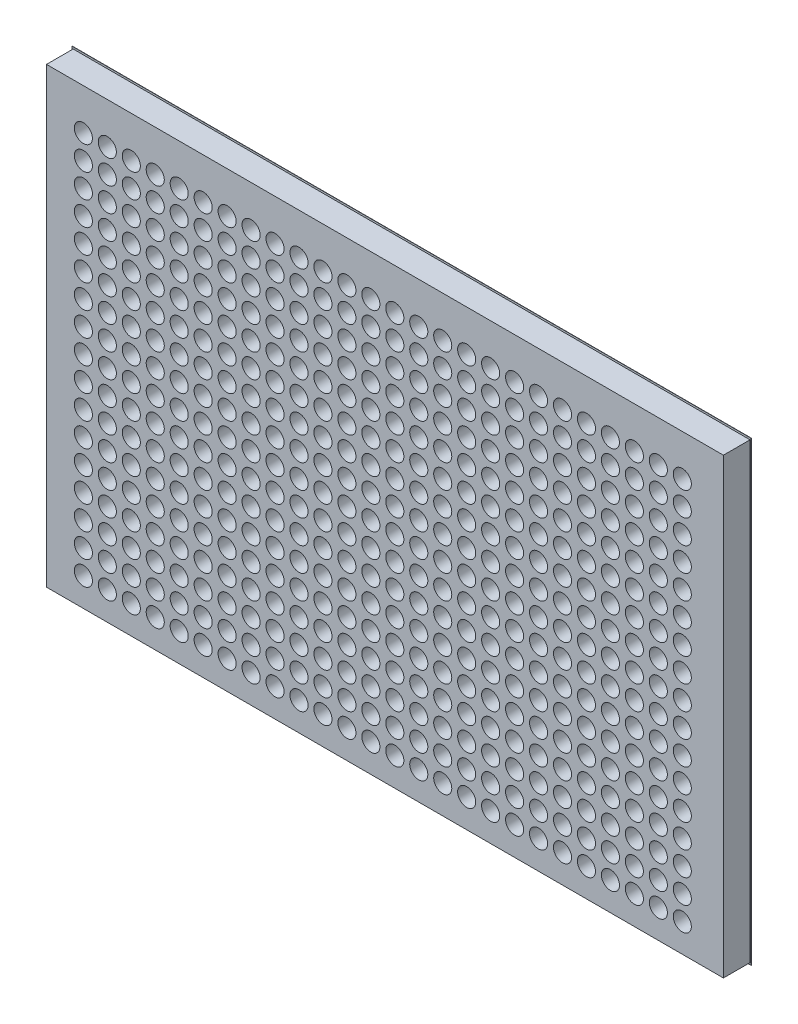
SolidWorks part; units mm, degrees
ref_plane "Front Plane" through (0, 0, 0) normal (0, 0, 1) x (1, 0, 0)
ref_plane "Top Plane" through (0, 0, 0) normal (0, 1, 0) x (1, 0, 0)
ref_plane "Right Plane" through (0, 0, 0) normal (1, 0, 0) x (0, 0, -1)
sketch "Sketch2" plane through (0, 0, 0) normal (0, 0, 1) x (1, 0, 0)
  line L1 (-127.6, -85.75) -> (127.6, -85.75)
  line L2 (-127.6, -85.75) -> (-127.6, 85.75)
  line L3 (-127.6, 85.75) -> (127.6, 85.75)
  line L4 (127.6, -85.75) -> (127.6, 85.75)
  line L5 (-127.6, -85.75) -> (127.6, 85.75) construction
  line L6 (-127.6, 85.75) -> (127.6, -85.75) construction
  point P0 (0, 0)
  dimension "D1" = 171.5
  dimension "D2" = 255.2
extrude "Boss-Extrude2" add sketch "Sketch2" along normal blind 0.1
sketch "Sketch3" plane through (0, 0, 0.1) normal (0, 0, 1) x (1, 0, 0)
  line L1 (-127.15, -85.05) -> (127.15, -85.05)
  line L2 (-127.15, -85.05) -> (-127.15, 85.05)
  line L3 (-127.15, 85.05) -> (127.15, 85.05)
  line L4 (127.15, -85.05) -> (127.15, 85.05)
  line L5 (-127.15, -85.05) -> (127.15, 85.05) construction
  line L6 (-127.15, 85.05) -> (127.15, -85.05) construction
  point P0 (0, 0)
  dimension "D1" = 254.3
  dimension "D2" = 170.1
extrude "Boss-Extrude3" add sketch "Sketch3" along normal blind 10
sketch "Sketch4" plane through (0, 0, 10.1) normal (0, 0, 1) x (1, 0, 0)
  line L0 (-127.6, 85.75) -> (-127.6, -85.75) construction
  line L1 (-127.6, -85.75) -> (127.6, -85.75) construction
  circle A0 centre (-113.3, -74.39) radius 3.4
  circle A96 centre (-104.3, -74.39) radius 3.4
  circle A97 centre (-95.3, -74.39) radius 3.4
  circle A98 centre (-86.3, -74.39) radius 3.4
  circle A99 centre (-77.3, -74.39) radius 3.4
  circle A100 centre (-68.3, -74.39) radius 3.4
  circle A101 centre (-59.3, -74.39) radius 3.4
  circle A102 centre (-50.3, -74.39) radius 3.4
  circle A103 centre (-41.3, -74.39) radius 3.4
  circle A104 centre (-32.3, -74.39) radius 3.4
  circle A105 centre (-23.3, -74.39) radius 3.4
  circle A106 centre (-14.3, -74.39) radius 3.4
  circle A107 centre (-5.3, -74.39) radius 3.4
  circle A108 centre (3.7, -74.39) radius 3.4
  circle A109 centre (12.7, -74.39) radius 3.4
  circle A110 centre (21.7, -74.39) radius 3.4
  circle A111 centre (30.7, -74.39) radius 3.4
  circle A112 centre (39.7, -74.39) radius 3.4
  circle A113 centre (48.7, -74.39) radius 3.4
  circle A114 centre (57.7, -74.39) radius 3.4
  circle A115 centre (66.7, -74.39) radius 3.4
  circle A116 centre (75.7, -74.39) radius 3.4
  circle A117 centre (84.7, -74.39) radius 3.4
  circle A118 centre (93.7, -74.39) radius 3.4
  circle A119 centre (102.7, -74.39) radius 3.4
  circle A120 centre (111.7, -74.39) radius 3.4
  circle A121 centre (-104.3, -65.39) radius 3.4
  circle A122 centre (-95.3, -65.39) radius 3.4
  circle A123 centre (-86.3, -65.39) radius 3.4
  circle A124 centre (-77.3, -65.39) radius 3.4
  circle A125 centre (-68.3, -65.39) radius 3.4
  circle A126 centre (-59.3, -65.39) radius 3.4
  circle A127 centre (-50.3, -65.39) radius 3.4
  circle A128 centre (-41.3, -65.39) radius 3.4
  circle A129 centre (-32.3, -65.39) radius 3.4
  circle A130 centre (-23.3, -65.39) radius 3.4
  circle A131 centre (-14.3, -65.39) radius 3.4
  circle A132 centre (-5.3, -65.39) radius 3.4
  circle A133 centre (3.7, -65.39) radius 3.4
  circle A134 centre (12.7, -65.39) radius 3.4
  circle A135 centre (21.7, -65.39) radius 3.4
  circle A136 centre (30.7, -65.39) radius 3.4
  circle A137 centre (39.7, -65.39) radius 3.4
  circle A138 centre (48.7, -65.39) radius 3.4
  circle A139 centre (57.7, -65.39) radius 3.4
  circle A140 centre (66.7, -65.39) radius 3.4
  circle A141 centre (75.7, -65.39) radius 3.4
  circle A142 centre (84.7, -65.39) radius 3.4
  circle A143 centre (93.7, -65.39) radius 3.4
  circle A144 centre (102.7, -65.39) radius 3.4
  circle A145 centre (111.7, -65.39) radius 3.4
  circle A146 centre (-104.3, -56.39) radius 3.4
  circle A147 centre (-95.3, -56.39) radius 3.4
  circle A148 centre (-86.3, -56.39) radius 3.4
  circle A149 centre (-77.3, -56.39) radius 3.4
  circle A150 centre (-68.3, -56.39) radius 3.4
  circle A151 centre (-59.3, -56.39) radius 3.4
  circle A152 centre (-50.3, -56.39) radius 3.4
  circle A153 centre (-41.3, -56.39) radius 3.4
  circle A154 centre (-32.3, -56.39) radius 3.4
  circle A155 centre (-23.3, -56.39) radius 3.4
  circle A156 centre (-14.3, -56.39) radius 3.4
  circle A157 centre (-5.3, -56.39) radius 3.4
  circle A158 centre (3.7, -56.39) radius 3.4
  circle A159 centre (12.7, -56.39) radius 3.4
  circle A160 centre (21.7, -56.39) radius 3.4
  circle A161 centre (30.7, -56.39) radius 3.4
  circle A162 centre (39.7, -56.39) radius 3.4
  circle A163 centre (48.7, -56.39) radius 3.4
  circle A164 centre (57.7, -56.39) radius 3.4
  circle A165 centre (66.7, -56.39) radius 3.4
  circle A166 centre (75.7, -56.39) radius 3.4
  circle A167 centre (84.7, -56.39) radius 3.4
  circle A168 centre (93.7, -56.39) radius 3.4
  circle A169 centre (102.7, -56.39) radius 3.4
  circle A170 centre (111.7, -56.39) radius 3.4
  circle A171 centre (-104.3, -47.39) radius 3.4
  circle A172 centre (-95.3, -47.39) radius 3.4
  circle A173 centre (-86.3, -47.39) radius 3.4
  circle A174 centre (-77.3, -47.39) radius 3.4
  circle A175 centre (-68.3, -47.39) radius 3.4
  circle A176 centre (-59.3, -47.39) radius 3.4
  circle A177 centre (-50.3, -47.39) radius 3.4
  circle A178 centre (-41.3, -47.39) radius 3.4
  circle A179 centre (-32.3, -47.39) radius 3.4
  circle A180 centre (-23.3, -47.39) radius 3.4
  circle A181 centre (-14.3, -47.39) radius 3.4
  circle A182 centre (-5.3, -47.39) radius 3.4
  circle A183 centre (3.7, -47.39) radius 3.4
  circle A184 centre (12.7, -47.39) radius 3.4
  circle A185 centre (21.7, -47.39) radius 3.4
  circle A186 centre (30.7, -47.39) radius 3.4
  circle A187 centre (39.7, -47.39) radius 3.4
  circle A188 centre (48.7, -47.39) radius 3.4
  circle A189 centre (57.7, -47.39) radius 3.4
  circle A190 centre (66.7, -47.39) radius 3.4
  circle A191 centre (75.7, -47.39) radius 3.4
  circle A192 centre (84.7, -47.39) radius 3.4
  circle A193 centre (93.7, -47.39) radius 3.4
  circle A194 centre (102.7, -47.39) radius 3.4
  circle A195 centre (111.7, -47.39) radius 3.4
  circle A196 centre (-104.3, -38.39) radius 3.4
  circle A197 centre (-95.3, -38.39) radius 3.4
  circle A198 centre (-86.3, -38.39) radius 3.4
  circle A199 centre (-77.3, -38.39) radius 3.4
  circle A200 centre (-68.3, -38.39) radius 3.4
  circle A201 centre (-59.3, -38.39) radius 3.4
  circle A202 centre (-50.3, -38.39) radius 3.4
  circle A203 centre (-41.3, -38.39) radius 3.4
  circle A204 centre (-32.3, -38.39) radius 3.4
  circle A205 centre (-23.3, -38.39) radius 3.4
  circle A206 centre (-14.3, -38.39) radius 3.4
  circle A207 centre (-5.3, -38.39) radius 3.4
  circle A208 centre (3.7, -38.39) radius 3.4
  circle A209 centre (12.7, -38.39) radius 3.4
  circle A210 centre (21.7, -38.39) radius 3.4
  circle A211 centre (30.7, -38.39) radius 3.4
  circle A212 centre (39.7, -38.39) radius 3.4
  circle A213 centre (48.7, -38.39) radius 3.4
  circle A214 centre (57.7, -38.39) radius 3.4
  circle A215 centre (66.7, -38.39) radius 3.4
  circle A216 centre (75.7, -38.39) radius 3.4
  circle A217 centre (84.7, -38.39) radius 3.4
  circle A218 centre (93.7, -38.39) radius 3.4
  circle A219 centre (102.7, -38.39) radius 3.4
  circle A220 centre (111.7, -38.39) radius 3.4
  circle A221 centre (-104.3, -29.39) radius 3.4
  circle A222 centre (-95.3, -29.39) radius 3.4
  circle A223 centre (-86.3, -29.39) radius 3.4
  circle A224 centre (-77.3, -29.39) radius 3.4
  circle A225 centre (-68.3, -29.39) radius 3.4
  circle A226 centre (-59.3, -29.39) radius 3.4
  circle A227 centre (-50.3, -29.39) radius 3.4
  circle A228 centre (-41.3, -29.39) radius 3.4
  circle A229 centre (-32.3, -29.39) radius 3.4
  circle A230 centre (-23.3, -29.39) radius 3.4
  circle A231 centre (-14.3, -29.39) radius 3.4
  circle A232 centre (-5.3, -29.39) radius 3.4
  circle A233 centre (3.7, -29.39) radius 3.4
  circle A234 centre (12.7, -29.39) radius 3.4
  circle A235 centre (21.7, -29.39) radius 3.4
  circle A236 centre (30.7, -29.39) radius 3.4
  circle A237 centre (39.7, -29.39) radius 3.4
  circle A238 centre (48.7, -29.39) radius 3.4
  circle A239 centre (57.7, -29.39) radius 3.4
  circle A240 centre (66.7, -29.39) radius 3.4
  circle A241 centre (75.7, -29.39) radius 3.4
  circle A242 centre (84.7, -29.39) radius 3.4
  circle A243 centre (93.7, -29.39) radius 3.4
  circle A244 centre (102.7, -29.39) radius 3.4
  circle A245 centre (111.7, -29.39) radius 3.4
  circle A246 centre (-104.3, -20.39) radius 3.4
  circle A247 centre (-95.3, -20.39) radius 3.4
  circle A248 centre (-86.3, -20.39) radius 3.4
  circle A249 centre (-77.3, -20.39) radius 3.4
  circle A250 centre (-68.3, -20.39) radius 3.4
  circle A251 centre (-59.3, -20.39) radius 3.4
  circle A252 centre (-50.3, -20.39) radius 3.4
  circle A253 centre (-41.3, -20.39) radius 3.4
  circle A254 centre (-32.3, -20.39) radius 3.4
  circle A255 centre (-23.3, -20.39) radius 3.4
  circle A256 centre (-14.3, -20.39) radius 3.4
  circle A257 centre (-5.3, -20.39) radius 3.4
  circle A258 centre (3.7, -20.39) radius 3.4
  circle A259 centre (12.7, -20.39) radius 3.4
  circle A260 centre (21.7, -20.39) radius 3.4
  circle A261 centre (30.7, -20.39) radius 3.4
  circle A262 centre (39.7, -20.39) radius 3.4
  circle A263 centre (48.7, -20.39) radius 3.4
  circle A264 centre (57.7, -20.39) radius 3.4
  circle A265 centre (66.7, -20.39) radius 3.4
  circle A266 centre (75.7, -20.39) radius 3.4
  circle A267 centre (84.7, -20.39) radius 3.4
  circle A268 centre (93.7, -20.39) radius 3.4
  circle A269 centre (102.7, -20.39) radius 3.4
  circle A270 centre (111.7, -20.39) radius 3.4
  circle A271 centre (-104.3, -11.39) radius 3.4
  circle A272 centre (-95.3, -11.39) radius 3.4
  circle A273 centre (-86.3, -11.39) radius 3.4
  circle A274 centre (-77.3, -11.39) radius 3.4
  circle A275 centre (-68.3, -11.39) radius 3.4
  circle A276 centre (-59.3, -11.39) radius 3.4
  circle A277 centre (-50.3, -11.39) radius 3.4
  circle A278 centre (-41.3, -11.39) radius 3.4
  circle A279 centre (-32.3, -11.39) radius 3.4
  circle A280 centre (-23.3, -11.39) radius 3.4
  circle A281 centre (-14.3, -11.39) radius 3.4
  circle A282 centre (-5.3, -11.39) radius 3.4
  circle A283 centre (3.7, -11.39) radius 3.4
  circle A284 centre (12.7, -11.39) radius 3.4
  circle A285 centre (21.7, -11.39) radius 3.4
  circle A286 centre (30.7, -11.39) radius 3.4
  circle A287 centre (39.7, -11.39) radius 3.4
  circle A288 centre (48.7, -11.39) radius 3.4
  circle A289 centre (57.7, -11.39) radius 3.4
  circle A290 centre (66.7, -11.39) radius 3.4
  circle A291 centre (75.7, -11.39) radius 3.4
  circle A292 centre (84.7, -11.39) radius 3.4
  circle A293 centre (93.7, -11.39) radius 3.4
  circle A294 centre (102.7, -11.39) radius 3.4
  circle A295 centre (111.7, -11.39) radius 3.4
  circle A296 centre (-104.3, -2.39) radius 3.4
  circle A297 centre (-95.3, -2.39) radius 3.4
  circle A298 centre (-86.3, -2.39) radius 3.4
  circle A299 centre (-77.3, -2.39) radius 3.4
  circle A300 centre (-68.3, -2.39) radius 3.4
  circle A301 centre (-59.3, -2.39) radius 3.4
  circle A302 centre (-50.3, -2.39) radius 3.4
  circle A303 centre (-41.3, -2.39) radius 3.4
  circle A304 centre (-32.3, -2.39) radius 3.4
  circle A305 centre (-23.3, -2.39) radius 3.4
  circle A306 centre (-14.3, -2.39) radius 3.4
  circle A307 centre (-5.3, -2.39) radius 3.4
  circle A308 centre (3.7, -2.39) radius 3.4
  circle A309 centre (12.7, -2.39) radius 3.4
  circle A310 centre (21.7, -2.39) radius 3.4
  circle A311 centre (30.7, -2.39) radius 3.4
  circle A312 centre (39.7, -2.39) radius 3.4
  circle A313 centre (48.7, -2.39) radius 3.4
  circle A314 centre (57.7, -2.39) radius 3.4
  circle A315 centre (66.7, -2.39) radius 3.4
  circle A316 centre (75.7, -2.39) radius 3.4
  circle A317 centre (84.7, -2.39) radius 3.4
  circle A318 centre (93.7, -2.39) radius 3.4
  circle A319 centre (102.7, -2.39) radius 3.4
  circle A320 centre (111.7, -2.39) radius 3.4
  circle A321 centre (-104.3, 6.61) radius 3.4
  circle A322 centre (-95.3, 6.61) radius 3.4
  circle A323 centre (-86.3, 6.61) radius 3.4
  circle A324 centre (-77.3, 6.61) radius 3.4
  circle A325 centre (-68.3, 6.61) radius 3.4
  circle A326 centre (-59.3, 6.61) radius 3.4
  circle A327 centre (-50.3, 6.61) radius 3.4
  circle A328 centre (-41.3, 6.61) radius 3.4
  circle A329 centre (-32.3, 6.61) radius 3.4
  circle A330 centre (-23.3, 6.61) radius 3.4
  circle A331 centre (-14.3, 6.61) radius 3.4
  circle A332 centre (-5.3, 6.61) radius 3.4
  circle A333 centre (3.7, 6.61) radius 3.4
  circle A334 centre (12.7, 6.61) radius 3.4
  circle A335 centre (21.7, 6.61) radius 3.4
  circle A336 centre (30.7, 6.61) radius 3.4
  circle A337 centre (39.7, 6.61) radius 3.4
  circle A338 centre (48.7, 6.61) radius 3.4
  circle A339 centre (57.7, 6.61) radius 3.4
  circle A340 centre (66.7, 6.61) radius 3.4
  circle A341 centre (75.7, 6.61) radius 3.4
  circle A342 centre (84.7, 6.61) radius 3.4
  circle A343 centre (93.7, 6.61) radius 3.4
  circle A344 centre (102.7, 6.61) radius 3.4
  circle A345 centre (111.7, 6.61) radius 3.4
  circle A346 centre (-104.3, 15.61) radius 3.4
  circle A347 centre (-95.3, 15.61) radius 3.4
  circle A348 centre (-86.3, 15.61) radius 3.4
  circle A349 centre (-77.3, 15.61) radius 3.4
  circle A350 centre (-68.3, 15.61) radius 3.4
  circle A351 centre (-59.3, 15.61) radius 3.4
  circle A352 centre (-50.3, 15.61) radius 3.4
  circle A353 centre (-41.3, 15.61) radius 3.4
  circle A354 centre (-32.3, 15.61) radius 3.4
  circle A355 centre (-23.3, 15.61) radius 3.4
  circle A356 centre (-14.3, 15.61) radius 3.4
  circle A357 centre (-5.3, 15.61) radius 3.4
  circle A358 centre (3.7, 15.61) radius 3.4
  circle A359 centre (12.7, 15.61) radius 3.4
  circle A360 centre (21.7, 15.61) radius 3.4
  circle A361 centre (30.7, 15.61) radius 3.4
  circle A362 centre (39.7, 15.61) radius 3.4
  circle A363 centre (48.7, 15.61) radius 3.4
  circle A364 centre (57.7, 15.61) radius 3.4
  circle A365 centre (66.7, 15.61) radius 3.4
  circle A366 centre (75.7, 15.61) radius 3.4
  circle A367 centre (84.7, 15.61) radius 3.4
  circle A368 centre (93.7, 15.61) radius 3.4
  circle A369 centre (102.7, 15.61) radius 3.4
  circle A370 centre (111.7, 15.61) radius 3.4
  circle A371 centre (-104.3, 24.61) radius 3.4
  circle A372 centre (-95.3, 24.61) radius 3.4
  circle A373 centre (-86.3, 24.61) radius 3.4
  circle A374 centre (-77.3, 24.61) radius 3.4
  circle A375 centre (-68.3, 24.61) radius 3.4
  circle A376 centre (-59.3, 24.61) radius 3.4
  circle A377 centre (-50.3, 24.61) radius 3.4
  circle A378 centre (-41.3, 24.61) radius 3.4
  circle A379 centre (-32.3, 24.61) radius 3.4
  circle A380 centre (-23.3, 24.61) radius 3.4
  circle A381 centre (-14.3, 24.61) radius 3.4
  circle A382 centre (-5.3, 24.61) radius 3.4
  circle A383 centre (3.7, 24.61) radius 3.4
  circle A384 centre (12.7, 24.61) radius 3.4
  circle A385 centre (21.7, 24.61) radius 3.4
  circle A386 centre (30.7, 24.61) radius 3.4
  circle A387 centre (39.7, 24.61) radius 3.4
  circle A388 centre (48.7, 24.61) radius 3.4
  circle A389 centre (57.7, 24.61) radius 3.4
  circle A390 centre (66.7, 24.61) radius 3.4
  circle A391 centre (75.7, 24.61) radius 3.4
  circle A392 centre (84.7, 24.61) radius 3.4
  circle A393 centre (93.7, 24.61) radius 3.4
  circle A394 centre (102.7, 24.61) radius 3.4
  circle A395 centre (111.7, 24.61) radius 3.4
  circle A396 centre (-104.3, 33.61) radius 3.4
  circle A397 centre (-95.3, 33.61) radius 3.4
  circle A398 centre (-86.3, 33.61) radius 3.4
  circle A399 centre (-77.3, 33.61) radius 3.4
  circle A400 centre (-68.3, 33.61) radius 3.4
  circle A401 centre (-59.3, 33.61) radius 3.4
  circle A402 centre (-50.3, 33.61) radius 3.4
  circle A403 centre (-41.3, 33.61) radius 3.4
  circle A404 centre (-32.3, 33.61) radius 3.4
  circle A405 centre (-23.3, 33.61) radius 3.4
  circle A406 centre (-14.3, 33.61) radius 3.4
  circle A407 centre (-5.3, 33.61) radius 3.4
  circle A408 centre (3.7, 33.61) radius 3.4
  circle A409 centre (12.7, 33.61) radius 3.4
  circle A410 centre (21.7, 33.61) radius 3.4
  circle A411 centre (30.7, 33.61) radius 3.4
  circle A412 centre (39.7, 33.61) radius 3.4
  circle A413 centre (48.7, 33.61) radius 3.4
  circle A414 centre (57.7, 33.61) radius 3.4
  circle A415 centre (66.7, 33.61) radius 3.4
  circle A416 centre (75.7, 33.61) radius 3.4
  circle A417 centre (84.7, 33.61) radius 3.4
  circle A418 centre (93.7, 33.61) radius 3.4
  circle A419 centre (102.7, 33.61) radius 3.4
  circle A420 centre (111.7, 33.61) radius 3.4
  circle A421 centre (-104.3, 42.61) radius 3.4
  circle A422 centre (-95.3, 42.61) radius 3.4
  circle A423 centre (-86.3, 42.61) radius 3.4
  circle A424 centre (-77.3, 42.61) radius 3.4
  circle A425 centre (-68.3, 42.61) radius 3.4
  circle A426 centre (-59.3, 42.61) radius 3.4
  circle A427 centre (-50.3, 42.61) radius 3.4
  circle A428 centre (-41.3, 42.61) radius 3.4
  circle A429 centre (-32.3, 42.61) radius 3.4
  circle A430 centre (-23.3, 42.61) radius 3.4
  circle A431 centre (-14.3, 42.61) radius 3.4
  circle A432 centre (-5.3, 42.61) radius 3.4
  circle A433 centre (3.7, 42.61) radius 3.4
  circle A434 centre (12.7, 42.61) radius 3.4
  circle A435 centre (21.7, 42.61) radius 3.4
  circle A436 centre (30.7, 42.61) radius 3.4
  circle A437 centre (39.7, 42.61) radius 3.4
  circle A438 centre (48.7, 42.61) radius 3.4
  circle A439 centre (57.7, 42.61) radius 3.4
  circle A440 centre (66.7, 42.61) radius 3.4
  circle A441 centre (75.7, 42.61) radius 3.4
  circle A442 centre (84.7, 42.61) radius 3.4
  circle A443 centre (93.7, 42.61) radius 3.4
  circle A444 centre (102.7, 42.61) radius 3.4
  circle A445 centre (111.7, 42.61) radius 3.4
  circle A446 centre (-104.3, 51.61) radius 3.4
  circle A447 centre (-95.3, 51.61) radius 3.4
  circle A448 centre (-86.3, 51.61) radius 3.4
  circle A449 centre (-77.3, 51.61) radius 3.4
  circle A450 centre (-68.3, 51.61) radius 3.4
  circle A451 centre (-59.3, 51.61) radius 3.4
  circle A452 centre (-50.3, 51.61) radius 3.4
  circle A453 centre (-41.3, 51.61) radius 3.4
  circle A454 centre (-32.3, 51.61) radius 3.4
  circle A455 centre (-23.3, 51.61) radius 3.4
  circle A456 centre (-14.3, 51.61) radius 3.4
  circle A457 centre (-5.3, 51.61) radius 3.4
  circle A458 centre (3.7, 51.61) radius 3.4
  circle A459 centre (12.7, 51.61) radius 3.4
  circle A460 centre (21.7, 51.61) radius 3.4
  circle A461 centre (30.7, 51.61) radius 3.4
  circle A462 centre (39.7, 51.61) radius 3.4
  circle A463 centre (48.7, 51.61) radius 3.4
  circle A464 centre (57.7, 51.61) radius 3.4
  circle A465 centre (66.7, 51.61) radius 3.4
  circle A466 centre (75.7, 51.61) radius 3.4
  circle A467 centre (84.7, 51.61) radius 3.4
  circle A468 centre (93.7, 51.61) radius 3.4
  circle A469 centre (102.7, 51.61) radius 3.4
  circle A470 centre (111.7, 51.61) radius 3.4
  circle A471 centre (-104.3, 60.61) radius 3.4
  circle A472 centre (-95.3, 60.61) radius 3.4
  circle A473 centre (-86.3, 60.61) radius 3.4
  circle A474 centre (-77.3, 60.61) radius 3.4
  circle A475 centre (-68.3, 60.61) radius 3.4
  circle A476 centre (-59.3, 60.61) radius 3.4
  circle A477 centre (-50.3, 60.61) radius 3.4
  circle A478 centre (-41.3, 60.61) radius 3.4
  circle A479 centre (-32.3, 60.61) radius 3.4
  circle A480 centre (-23.3, 60.61) radius 3.4
  circle A481 centre (-14.3, 60.61) radius 3.4
  circle A482 centre (-5.3, 60.61) radius 3.4
  circle A483 centre (3.7, 60.61) radius 3.4
  circle A484 centre (12.7, 60.61) radius 3.4
  circle A485 centre (21.7, 60.61) radius 3.4
  circle A486 centre (30.7, 60.61) radius 3.4
  circle A487 centre (39.7, 60.61) radius 3.4
  circle A488 centre (48.7, 60.61) radius 3.4
  circle A489 centre (57.7, 60.61) radius 3.4
  circle A490 centre (66.7, 60.61) radius 3.4
  circle A491 centre (75.7, 60.61) radius 3.4
  circle A492 centre (84.7, 60.61) radius 3.4
  circle A493 centre (93.7, 60.61) radius 3.4
  circle A494 centre (102.7, 60.61) radius 3.4
  circle A495 centre (111.7, 60.61) radius 3.4
  circle A496 centre (-104.3, 69.61) radius 3.4
  circle A497 centre (-95.3, 69.61) radius 3.4
  circle A498 centre (-86.3, 69.61) radius 3.4
  circle A499 centre (-77.3, 69.61) radius 3.4
  circle A500 centre (-68.3, 69.61) radius 3.4
  circle A501 centre (-59.3, 69.61) radius 3.4
  circle A502 centre (-50.3, 69.61) radius 3.4
  circle A503 centre (-41.3, 69.61) radius 3.4
  circle A504 centre (-32.3, 69.61) radius 3.4
  circle A505 centre (-23.3, 69.61) radius 3.4
  circle A506 centre (-14.3, 69.61) radius 3.4
  circle A507 centre (-5.3, 69.61) radius 3.4
  circle A508 centre (3.7, 69.61) radius 3.4
  circle A509 centre (12.7, 69.61) radius 3.4
  circle A510 centre (21.7, 69.61) radius 3.4
  circle A511 centre (30.7, 69.61) radius 3.4
  circle A512 centre (39.7, 69.61) radius 3.4
  circle A513 centre (48.7, 69.61) radius 3.4
  circle A514 centre (57.7, 69.61) radius 3.4
  circle A515 centre (66.7, 69.61) radius 3.4
  circle A516 centre (75.7, 69.61) radius 3.4
  circle A517 centre (84.7, 69.61) radius 3.4
  circle A518 centre (93.7, 69.61) radius 3.4
  circle A519 centre (102.7, 69.61) radius 3.4
  circle A520 centre (111.7, 69.61) radius 3.4
  circle A521 centre (-113.3, -65.39) radius 3.4
  circle A522 centre (-113.3, -56.39) radius 3.4
  circle A523 centre (-113.3, -47.39) radius 3.4
  circle A524 centre (-113.3, -38.39) radius 3.4
  circle A525 centre (-113.3, -29.39) radius 3.4
  circle A526 centre (-113.3, -20.39) radius 3.4
  circle A527 centre (-113.3, -11.39) radius 3.4
  circle A528 centre (-113.3, -2.39) radius 3.4
  circle A529 centre (-113.3, 6.61) radius 3.4
  circle A530 centre (-113.3, 15.61) radius 3.4
  circle A531 centre (-113.3, 24.61) radius 3.4
  circle A532 centre (-113.3, 33.61) radius 3.4
  circle A533 centre (-113.3, 42.61) radius 3.4
  circle A534 centre (-113.3, 51.61) radius 3.4
  circle A535 centre (-113.3, 60.61) radius 3.4
  circle A536 centre (-113.3, 69.61) radius 3.4
  dimension "D3" = 6.8
  dimension "D1" = 14.3
  dimension "D2" = 11.36
  dimension "D4" = 26
  dimension "D5" = 17
extrude "Cut-Extrude2" cut sketch "Sketch4" along direction (0, 0, -1) on the side against the normal up to next (10.1 mm away)
